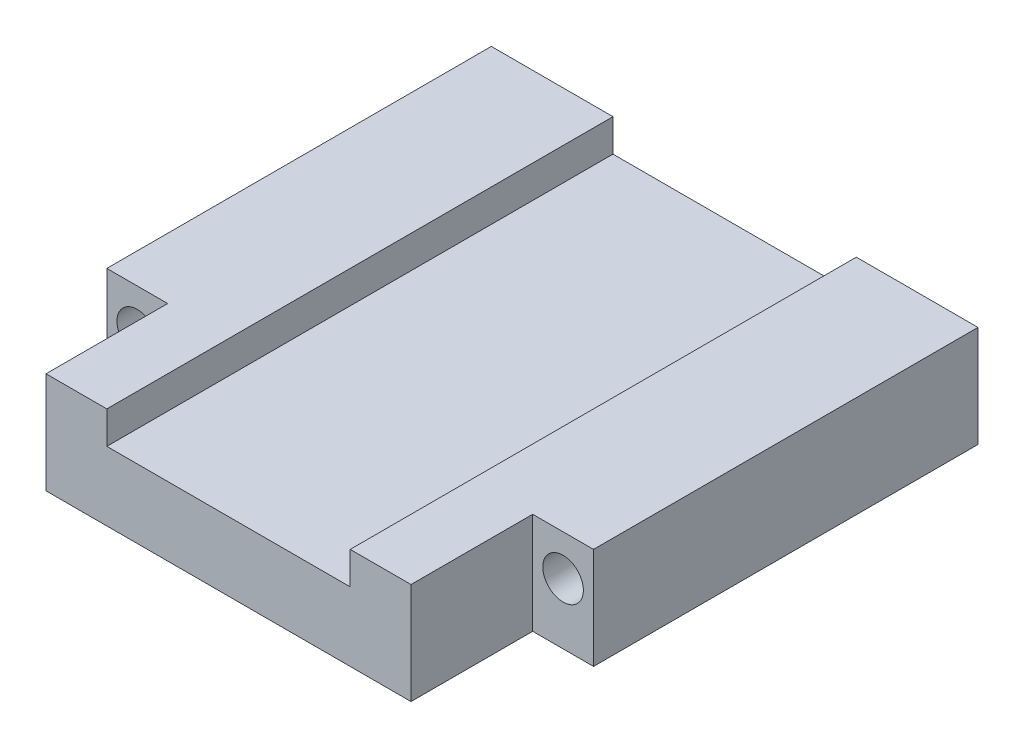
SolidWorks part; units mm, degrees
material "6063-O"
ref_plane "Front" through (0, 0, 0) normal (0, 0, 1) x (1, 0, 0)
ref_plane "Top" through (0, 0, 0) normal (0, 1, 0) x (1, 0, 0)
ref_plane "Right" through (0, 0, 0) normal (1, 0, 0) x (0, 0, -1)
sketch "Sketch1" plane through (0, 0, 0) normal (0, 0, 1) x (1, 0, 0)
  line L1 (19.05, -3.9687) -> (-19.05, -3.9688)
  line L2 (19.05, -3.9687) -> (19.05, 3.9688)
  line L3 (19.05, 3.9688) -> (-19.05, 3.9687)
  line L4 (-19.05, -3.9688) -> (-19.05, 3.9687)
  line L5 (19.05, -3.9687) -> (-19.05, 3.9687) construction
  line L6 (19.05, 3.9688) -> (-19.05, -3.9688) construction
  point P0 (0, 0)
  dimension "D1" = 7.9375
  dimension "D2" = 38.1
extrude "Boss-Extrude1" add sketch "Sketch1" along normal blind 39.624
sketch "Sketch2" plane through (0, 0, 39.624) normal (0, 0, 1) x (1, 0, 0)
  line L0 (9.525, 3.9688) -> (9.525, 1.4288)
  line L1 (19.05, 3.9688) -> (-19.05, 3.9687) construction
  line L2 (9.525, 1.4288) -> (-9.525, 1.4288)
  line L3 (-9.525, 1.4288) -> (-9.525, 3.9688)
  line L4 (-9.525, 3.9688) -> (9.525, 3.9688)
  line L5 (0, 0) -> (0, 21.8907) construction
  point P9 (0, 3.9688)
  dimension "D1" = 19.05
  dimension "D2" = 2.54
extrude "Cut-Extrude1" cut sketch "Sketch2" against normal through all
sketch "Sketch3" plane through (0, 0, 0) normal (0, 0, -1) x (-1, 0, 0)
  line L0 (-16.6687, 0.7938) -> (16.6687, 0.7938) construction
  line L3 (-19.05, 3.9688) -> (-9.525, 3.9688) construction
  line L4 (0, 0) -> (0, 0.7938) construction
  circle A0 centre (-16.6687, 0.7938) radius 1.5875
  circle A2 centre (16.6687, 0.7938) radius 1.5875
  dimension "D3" = 3.175
  dimension "D2" = 33.3375
  dimension "D1" = 3.175
hole_wizard "1/8 (0.125) Clearance Dowel Hole1" positions "Sketch7" profile "Sketch8" hole size "1/8" standard "ANSI Inch" end condition through all
sketch "Sketch7" plane through (0, 0, 0) normal (0, 0, -1) x (-1, 0, 0)
  point P0 (-16.6687, 0.7938)
  point P3 (16.6687, 0.7938)
sketch "Sketch8" plane through (16.6687, 0.7938, 0) normal (1, 0, 0) x (0, 1, 0)
  line L0 (0, 0) -> (0, 39.624)
  line L1 (0, 39.624) -> (1.5875, 39.624)
  line L2 (1.5875, 39.624) -> (1.5875, 0)
  line L5 (1.5875, 0) -> (0, 0)
  line L11 (0, -6.35) -> (0, 107.95) construction
  dimension "Thru Hole Dia." = 3.175
  dimension "Thru Hole Depth" = 39.624
sketch "Sketch6" plane through (0, 0, 39.624) normal (0, 0, 1) x (1, 0, 0)
  line L0 (-19.05, -3.9688) -> (19.05, -3.9687) construction
  line L1 (-19.05, 3.9687) -> (-14.2875, 3.9687)
  line L2 (-19.05, 3.9687) -> (-19.05, -3.9688)
  line L3 (-19.05, -3.9688) -> (-14.2875, -3.9688)
  line L4 (-14.2875, 3.9687) -> (-14.2875, -3.9688)
  line L6 (19.05, 3.9688) -> (14.2875, 3.9687)
  line L7 (19.05, 3.9688) -> (19.05, -3.9687)
  line L8 (19.05, -3.9687) -> (14.2875, -3.9688)
  line L9 (14.2875, 3.9687) -> (14.2875, -3.9688)
  dimension "D1" = 4.7625
extrude "Cut-Extrude2" cut sketch "Sketch6" against normal blind 9.525
